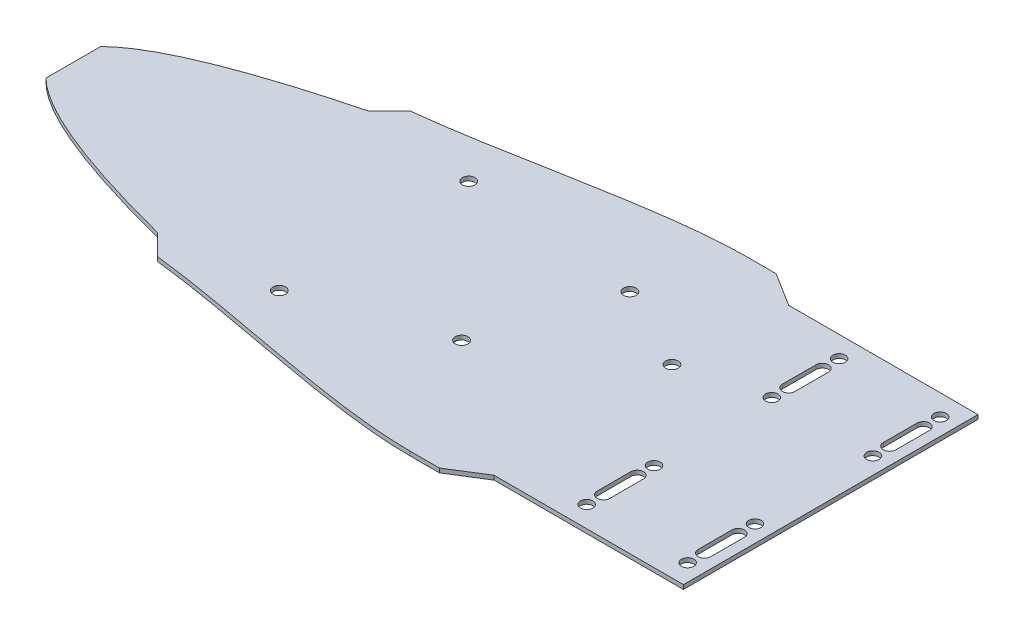
SolidWorks part; units mm, degrees
material "1060 Сплав"
ref_plane "Спереди" through (0, 0, 0) normal (0, 0, 1) x (1, 0, 0)
ref_plane "Сверху" through (0, 0, 0) normal (0, 1, 0) x (1, 0, 0)
ref_plane "Справа" through (0, 0, 0) normal (1, 0, 0) x (0, 0, -1)
sketch "Эскиз1" plane through (0, 0, 0) normal (0, 1, 0) x (1, 0, 0)
  line L0 (-109.2342, 0) -> (114.1892, 0) construction
  line L1 (90, -40) -> (-90, -40)
  line L2 (90, -40) -> (90, 40)
  line L3 (90, 40) -> (-90, 40)
  line L4 (-90, -40) -> (-90, 40)
  line L5 (90, -40) -> (-90, 40) construction
  line L6 (90, 40) -> (-90, -40) construction
  line L7 (45, 35) -> (37, 40)
  line L8 (90, 40) -> (45, 40)
  line L9 (90, 40) -> (90, 35)
  line L10 (90, 35) -> (45, 35)
  line L11 (45, 40) -> (45, 35)
  line L12 (90, -40) -> (45, -40)
  line L13 (90, -40) -> (90, -35)
  line L14 (90, -35) -> (45, -35)
  line L15 (45, -40) -> (45, -35)
  line L16 (45, -35) -> (37, -40)
  point P0 (0, 0)
  dimension "D1" = 180
  dimension "D2" = 80
  dimension "D3" = 45
  dimension "D4" = 70
  dimension "D5" = 8
extrude "Габариты" add sketch "Эскиз1" along normal blind 1 contours L16 L14 L2 L10 L7 L3 L4 L1 region at (-2.3054, 0, 0)
sketch "Эскиз2" plane through (0, 0, 0) normal (0, 1, 0) x (1, 0, 0)
  line L0 (-115.1505, 0) -> (106.9824, 0) construction
  line L1 (-90, -40) -> (-90, 40) construction
  line L2 (-90, 6.4911) -> (-90, -6.4911)
  line L3 (-90, 6.4911) -> (-90, -6.4911)
  line L5 (37, 40) -> (-90, 40) construction
  line L6 (37, -40) -> (-90, -40) construction
  line L7 (30, 40) -> (-90, 40)
  line L9 (-90, 40) -> (-90, 6.4911)
  line L10 (-90, -6.4911) -> (-90, -40)
  line L11 (-90, -40) -> (30, -40)
  line L12 (-45, 25.0267) -> (-40, 30)
  line L13 (-45, -25.0267) -> (-40, -30)
  parabola Q0 (30, -40) -> (30, 40) focus (-90, 0) apex (-93.2456, 0)
  spline S0 degree 3 poles (-40, 30) (-18.1065, 32.3885) (9.7804, 40) (30, 40) knots 0 0 0 0 1 1 1 1
  spline S1 degree 3 poles (-40, -30) (-18.1065, -32.3885) (9.7804, -40) (30, -40) knots 0 0 0 0 1 1 1 1
  point P15 (-90, 0)
  dimension "D1" = 120
  dimension "D2" = 45
  dimension "D3" = 50
  dimension "D4" = 60
extrude "Форма основы" cut sketch "Эскиз2" along normal through all contours L9 Q0 L7 | L11 Q0 L10 region at (-57.6692, 0, 30.3594) region at (-57.6692, 0, -30.3594)
sketch "Эскиз3" plane through (0, 0, 0) normal (0, 1, 0) x (1, 0, 0)
  line L0 (-107.3808, 0) -> (106.9824, 0) construction
  line L1 (74, 38.7487) -> (74, -39.5456) construction
  line L2 (90, 35) -> (45, 35) construction
  line L3 (62, 26) -> (62, 18) construction
  line L5 (63.5, 26) -> (63.5, 18)
  line L6 (60.5, 26) -> (60.5, 18)
  line L7 (86, 26) -> (86, 18) construction
  line L8 (84.5, 26) -> (84.5, 18)
  line L9 (87.5, 26) -> (87.5, 18)
  line L10 (62, -26) -> (62, -18) construction
  line L11 (63.5, -26) -> (63.5, -18)
  line L12 (60.5, -26) -> (60.5, -18)
  line L13 (86, -26) -> (86, -18) construction
  line L14 (84.5, -26) -> (84.5, -18)
  line L15 (87.5, -26) -> (87.5, -18)
  line L25 (90, -35) -> (90, 35) construction
  circle A0 centre (62, 30) radius 1.475
  circle A1 centre (62, 14) radius 1.475
  circle A2 centre (86, 14) radius 1.475
  circle A3 centre (86, 30) radius 1.475
  circle A4 centre (86, -14) radius 1.475
  circle A5 centre (86, -30) radius 1.475
  circle A6 centre (62, -14) radius 1.475
  circle A7 centre (62, -30) radius 1.475
  arc A8 (63.5, 26) -> (60.5, 26) centre (62, 26) ccw
  arc A9 (60.5, 18) -> (63.5, 18) centre (62, 18) ccw
  arc A10 (84.5, 26) -> (87.5, 26) centre (86, 26) cw
  arc A11 (87.5, 18) -> (84.5, 18) centre (86, 18) cw
  arc A12 (63.5, -26) -> (60.5, -26) centre (62, -26) cw
  arc A13 (60.5, -18) -> (63.5, -18) centre (62, -18) cw
  arc A14 (84.5, -26) -> (87.5, -26) centre (86, -26) ccw
  arc A15 (87.5, -18) -> (84.5, -18) centre (86, -18) ccw
  point P11 (62, 22)
  point P34 (86, 22)
  point P41 (62, -22)
  point P48 (86, -22)
  dimension "D2" = 2.95
  dimension "D1" = 16
  dimension "D3" = 24
  dimension "D4" = 16
  dimension "D5" = 5
  dimension "D6" = 4
  dimension "D7" = 4
  dimension "D8" = 3
extrude "Крепёж колёс" cut sketch "Эскиз3" along direction (0, 1, 0) on the side of the normal through all
sketch "Эскиз6" plane through (0, 1, 0) normal (0, 1, 0) x (1, 0, 0)
  circle A0 centre (23.3494, 18.9182) radius 1.5
  circle A1 centre (13.3494, -11.0818) radius 1.5
  circle A2 centre (43.3494, 8.9182) radius 1.5
  point P6 (7.8055, -10.4506)
  point P7 (43.3494, 8.9182)
  point P8 (40.5656, 9.2055)
  dimension "D1" = 20
  dimension "D5" = 3
  dimension "D2" = 10
  dimension "D3" = 30
  dimension "D4" = 10
extrude "Вырез для крепления платы" cut sketch "Эскиз6" against normal through all
sketch "Эскиз5" plane through (0, 0, 0) normal (0, 1, 0) x (1, 0, 0)
  line L0 (-94.6705, 0) -> (98.4358, 0) construction
  line L2 (-18.5413, 43.7441) -> (-18.5413, -40.7615) construction
  circle A3 centre (-18.5413, 22.5) radius 1.5
  circle A4 centre (-18.5413, -22.5) radius 1.5
  point P9 (0, 0)
  point P10 (-39.5564, 22.5)
  point P11 (-17.7269, 22.5)
  point P12 (-18.5413, 43.7441)
  dimension "D1" = 3
  dimension "D2" = 45
extrude "Крепёж датчиков" cut sketch "Эскиз5" along normal blind 3
